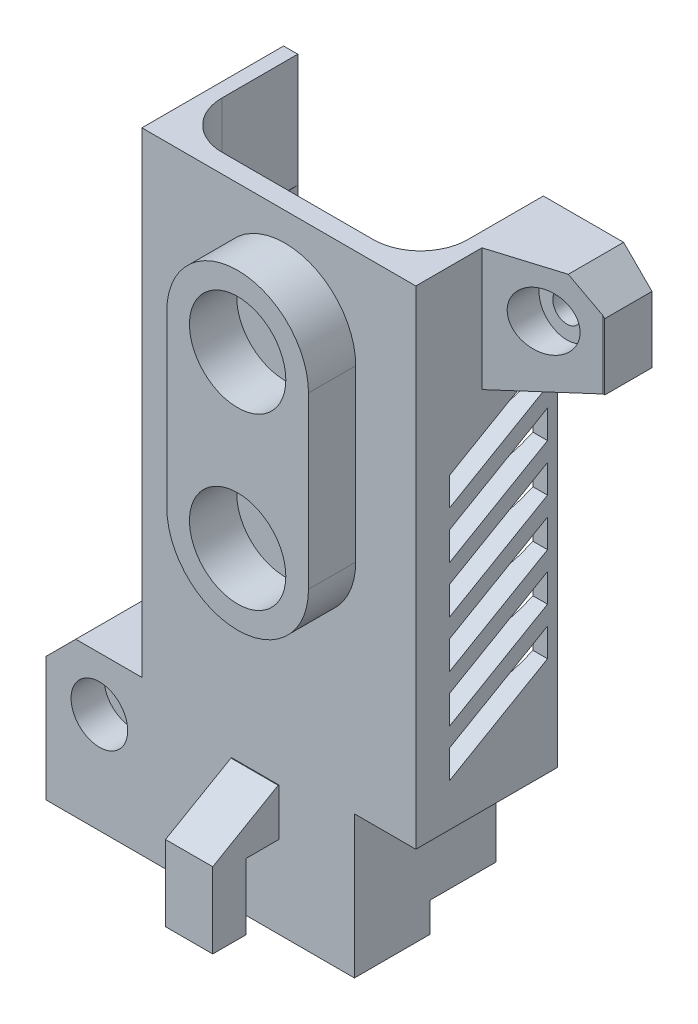
SolidWorks part; units mm, degrees
ref_plane "Přední rovina" through (0, 0, 0) normal (0, 0, 1) x (1, 0, 0)
ref_plane "Horní rovina" through (0, 0, 0) normal (0, 1, 0) x (1, 0, 0)
ref_plane "Pravá rovina" through (0, 0, 0) normal (1, 0, 0) x (0, 0, -1)
sketch "Skica2" plane through (0, 0, 0) normal (0, -1, 0) x (1, 0, 0)
  line L0 (8, 0) -> (6, 0)
  line L1 (-6, 0) -> (-8, 0)
  circle A0 centre (0, 0) radius 8 construction
  circle A1 centre (0, 0) radius 6 construction
  arc A2 (8, 0) -> (-8, 0) centre (0, 0) ccw
  arc A3 (6, 0) -> (-6, 0) centre (0, 0) ccw
extrude "Přidat vysunutím1" add sketch "Skica2" along normal up to surface (6 mm away)
sketch "Skica3" plane through (0, -9.7, 0) normal (0, -1, 0) x (1, 0, 0)
  line L0 (8, 0) -> (4.5, 0)
  line L1 (-4.5, 0) -> (-8, 0)
  line L2 (8, 0) -> (2, 0)
  line L3 (-2, 0) -> (-8, 0)
  circle A1 centre (0, 0) radius 8
  arc A2 (8, 0) -> (-8, 0) centre (0, 0) ccw
  arc A4 (2, 0) -> (-2, 0) centre (0, 0) ccw
  circle M2 centre (0, 0) radius 4.5
  circle M3 centre (0, 0) radius 8
  dimension "D1" = 0
extrude "Přidat vysunutím2" add sketch "Skica3" along normal up to surface (4 mm away) separate body contours A4 L2 L3 M2 | L1 L0 M2 M3 region at (6.25, -9.7, 0.1789) region at (0, -9.7, 2.171)
sketch "Skica4" plane through (0, 0, 0) normal (0, 0, -1) x (-1, 0, 0)
  circle A0 centre (-7.768, -14.6856) radius 4.1255
sketch "Skica6" plane through (0, -13.7, 0) normal (0, -1, 0) x (1, 0, 0)
  line L0 (-13, 0) -> (-8, 0)
  line L1 (8, 0) -> (13, 0)
  arc A0 (8, 0) -> (-8, 0) centre (0, 0) ccw construction
  arc A1 (8, 0) -> (-8, 0) centre (0, 0) ccw
  arc A2 (13, 0) -> (-13, 0) centre (0, 0) ccw
extrude "Přidat vysunutím3" add sketch "Skica6" against normal up to surface (18.7 mm away)
sketch "Skica7" plane through (0, 5, 0) normal (0, 1, 0) x (1, 0, 0)
  line L0 (-13, 0) -> (-14.5, 0)
  line L1 (-14.5, 0) -> (-14.5, -15)
  line L2 (-14.5, -15) -> (14.5, -15)
  line L3 (14.5, -15) -> (14.5, 0)
  line L4 (14.5, 0) -> (13, 0)
  arc A1 (-13, 0) -> (13, 0) centre (0, 0) ccw
extrude "Přidat vysunutím4" add sketch "Skica7" along normal up to surface (36 mm away) separate body
sketch "Skica8" plane through (0, 41, 0) normal (0, 1, 0) x (1, 0, 0)
  line L0 (-14.5, 0) -> (-13, 0) construction
  line L1 (13, 0) -> (21.5, 0) construction
  line L3 (-14.5, -15) -> (-14.5, 0) construction
  line L4 (14.5, -15) -> (-14.5, -15) construction
  line L5 (-14.5, 0) -> (-13, 0)
  line L6 (13, 0) -> (14.5, 0)
  line L7 (14.5, 0) -> (14.5, -15)
  line L8 (-14.5, -15) -> (-14.5, 0)
  line L9 (14.5, -15) -> (-14.5, -15)
  line L10 (-13, 0) -> (-13, -8)
  line L11 (-8, -13) -> (8, -13)
  line L12 (13, -8) -> (13, 0)
  arc A0 (-13, 0) -> (13, 0) centre (0, 0) ccw construction
  arc A1 (-13, -8) -> (-8, -13) centre (-8, -8) ccw
  arc A2 (8, -13) -> (13, -8) centre (8, -8) ccw
  dimension "D1" = 5
extrude "Přidat vysunutím5" add sketch "Skica8" along normal up to surface (12 mm away)
sketch "Skica9" plane through (0, 5, 0) normal (0, -1, 0) x (1, 0, 0)
  line L5 (13, 0) -> (14.5, 0)
  line L6 (14.5, 0) -> (14.5, 15)
  line L7 (14.5, 15) -> (-14.5, 15)
  line L8 (-14.5, 15) -> (-14.5, 0)
  line L9 (-14.5, 0) -> (-13, 0)
  line L10 (13, 0) -> (14.5, 0)
  line L11 (14.5, 0) -> (14.5, 15)
  line L12 (14.5, 15) -> (-14.5, 15)
  line L13 (-14.5, 15) -> (-14.5, 0)
  line L14 (-14.5, 0) -> (-13, 0)
  arc A1 (13, 0) -> (-13, 0) centre (0, 0) ccw
  arc A2 (13, 0) -> (-13, 0) centre (0, 0) ccw
  dimension "D1" = 0
extrude "Přidat vysunutím6" add sketch "Skica9" along normal up to surface (18.7 mm away) up to face at (0, -13.7, 3.75)
sketch "Skica10" plane through (0, 0, 0) normal (0, 0, -1) x (-1, 0, 0)
  line L0 (-14.5, -13.7) -> (-14.5, 53) construction
  line L1 (-14.5, 1.3549) -> (-8, 1.3549)
  line L2 (-14.5, 1.3549) -> (-14.5, -14.6856)
  line L3 (-14.5, -14.6856) -> (-8, -14.6856)
  line L4 (-8, 1.3549) -> (-8, -14.6856)
  line L5 (-14.5, 1.3549) -> (-8.0034, 1.3549) construction
  line L6 (-8, -6) -> (-8, -9.7) construction
extrude "Odebrat vysunutím2" cut sketch "Skica10" against normal up to surface (15 mm away) up to face at (0, 19.65, 15)
extrude "Odebrat vysunutím3" cut sketch "Skica4" against normal blind 7
sketch "Skica11" plane through (0, 0, 0) normal (0, 0, 1) x (1, 0, 0)
  line L17 (-24.65, -13.7) -> (-14.5, -13.7)
  line L18 (-14.5, -13.7) -> (-4.7569, -13.7)
  line L19 (-2.2431, -13.7) -> (-2, -13.7)
  line L20 (-2, -13.7) -> (-2, -9.7)
  line L21 (-2, -9.7) -> (-8, -9.7)
  line L22 (-8, -9.7) -> (-8, -6)
  line L23 (-8, -6) -> (-6, -6)
  line L24 (-6, -6) -> (-6, 0)
  line L25 (-6, 0) -> (-8, 0)
  line L26 (-8, 0) -> (-8, 5)
  line L27 (-8, 5) -> (-13, 5)
  line L28 (-13, 5) -> (-13, 10.9652)
  line L29 (-13, 10.9652) -> (-14.5, 10.9652)
  line L30 (-14.5, 10.9652) -> (-14.5, 2.6106)
  line L31 (-14.5, 2.6106) -> (-21.5034, 2.6106)
  line L32 (-21.5034, 2.6106) -> (-24.65, -0.5361)
  line L33 (-24.65, -0.5361) -> (-24.65, -13.7)
  line L34 (-24.65, -13.7) -> (-14.5, -13.7)
  line L35 (-14.5, -13.7) -> (-4.7569, -13.7)
  line L36 (-2.2431, -13.7) -> (-2, -13.7)
  line L37 (-2, -13.7) -> (-2, -9.7)
  line L38 (-2, -9.7) -> (-8, -9.7)
  line L39 (-8, -9.7) -> (-8, -6)
  line L40 (-8, -6) -> (-6, -6)
  line L41 (-6, -6) -> (-6, 0)
  line L42 (-6, 0) -> (-8, 0)
  line L43 (-8, 0) -> (-8, 5)
  line L44 (-8, 5) -> (-13, 5)
  line L45 (-13, 5) -> (-13, 10.9652)
  line L46 (-13, 10.9652) -> (-14.5, 10.9652)
  line L47 (-14.5, 10.9652) -> (-14.5, 2.6106)
  line L48 (-14.5, 2.6106) -> (-21.5034, 2.6106)
  line L49 (-21.5034, 2.6106) -> (-24.65, -0.5361)
  line L50 (-24.65, -0.5361) -> (-24.65, -13.7)
  arc A1 (-2.2431, -13.7) -> (-4.7569, -13.7) centre (-3.5, -18.5394) ccw
  arc A2 (-2.2431, -13.7) -> (-4.7569, -13.7) centre (-3.5, -18.5394) ccw
  circle A3 centre (-19, -3.0394) radius 1.6
  dimension "D1" = 0
extrude "Přidat vysunutím7" add sketch "Skica11" along normal up to surface (15 mm away) up to face at (2.6667, 13.5516, 15)
sketch "Skica12" plane through (0, 0, 0) normal (0, 0, -1) x (-1, 0, 0)
  circle A0 centre (3.5, -18.5394) radius 5
  dimension "D1" = 10
extrude "Odebrat vysunutím4" cut sketch "Skica12" against normal blind 10
sketch "Skica13" plane through (0, 0, 15) normal (0, 0, 1) x (1, 0, 0)
  circle A0 centre (-19, -3.0394) radius 3
  dimension "D1" = 6
extrude "Odebrat vysunutím5" cut sketch "Skica13" against normal blind 3.5
sketch "Skica14" plane through (14.5, 0, 0) normal (1, 0, 0) x (0, 0, -1)
  line L0 (-11.4494, 13.8487) -> (-1.0571, 19.8487)
  line L10 (-11.4494, 8.8487) -> (-1.0571, 14.8487)
  line L11 (-11.4494, 5.8487) -> (-11.4494, 8.8487)
  line L12 (-1.0571, 11.8487) -> (-11.4494, 5.8487)
  line L13 (-1.0571, 14.8487) -> (-1.0571, 11.8487)
  line L14 (-1.0571, 19.8487) -> (-1.0571, 16.8487)
  line L15 (-1.0571, 16.8487) -> (-11.4494, 10.8487)
  line L16 (-11.4494, 10.8487) -> (-11.4494, 13.8487)
  line L17 (-11.4494, 18.8487) -> (-1.0571, 24.8487)
  line L18 (-1.0571, 24.8487) -> (-1.0571, 21.8487)
  line L19 (-1.0571, 21.8487) -> (-11.4494, 15.8487)
  line L20 (-11.4494, 15.8487) -> (-11.4494, 18.8487)
  line L21 (-11.4494, 23.8487) -> (-1.0571, 29.8487)
  line L22 (-1.0571, 29.8487) -> (-1.0571, 26.8487)
  line L23 (-1.0571, 26.8487) -> (-11.4494, 20.8487)
  line L24 (-11.4494, 20.8487) -> (-11.4494, 23.8487)
  line L25 (-11.4494, 28.8487) -> (-1.0571, 34.8487)
  line L26 (-1.0571, 34.8487) -> (-1.0571, 31.8487)
  line L27 (-1.0571, 31.8487) -> (-11.4494, 25.8487)
  line L28 (-11.4494, 25.8487) -> (-11.4494, 28.8487)
  line L29 (-11.4494, 33.8487) -> (-1.0571, 39.8487)
  line L30 (-1.0571, 39.8487) -> (-1.0571, 36.8487)
  line L31 (-1.0571, 36.8487) -> (-11.4494, 30.8487)
  line L32 (-11.4494, 30.8487) -> (-11.4494, 33.8487)
  dimension "D1" = 6
extrude "Odebrat vysunutím6" cut sketch "Skica14" against normal up to surface (8.3428 mm away) up to face at (0, 26.6, 6.277)
sketch "Skica15" plane through (-14.5, 0, 0) normal (-1, 0, 0) x (0, 0, 1)
  line L0 (0, 10.9652) -> (0, 36.9652) construction
  circle A0 centre (-12, 35.9652) radius 1.5 construction
  circle A1 centre (-12, 11.9652) radius 1.5 construction
  arc A2 (0, 36.9652) -> (0, 10.9652) centre (0, 23.9652) ccw construction
  circle A6 centre (12, 35.9652) radius 1.5
  circle A7 centre (12, 11.9652) radius 1.5
extrude "Odebrat vysunutím7" cut sketch "Skica15" against normal up to surface (8 mm away)
sketch "Skica16" plane through (-14.5, 0, 0) normal (-1, 0, 0) x (0, 0, 1)
  line L0 (0, 10.9652) -> (0, 36.9652) construction
  arc A0 (0, 36.9652) -> (0, 10.9652) centre (0, 23.9652) ccw construction
  circle A1 centre (0, 23.9652) radius 13
extrude "Odebrat vysunutím8" cut sketch "Skica16" against normal up to surface (14.5 mm away) up to face at (-7.0789, 35.9027, 10.8818)
sketch "Skica17" plane through (14.5, 0, 0) normal (1, 0, 0) x (0, 0, -1)
  line L1 (0, 53) -> (-5, 53)
  line L2 (0, 53) -> (0, 43)
  line L3 (0, 43) -> (-5, 43)
  line L4 (-5, 53) -> (-5, 43)
  dimension "D1" = 10
  dimension "D2" = 5
extrude "Přidat vysunutím8" add sketch "Skica17" along normal blind 10
chamfer "Zkosení1" distance 3 angle 73 1 edges at (14.5, 43, 2.5) first distance on face at (14.5, 15.3487, 6.2533)
chamfer "Zkosení2" distance 3 angle 73 1 edges at (14.5, 46.5, 5) first distance on face at (14.5, 15.3487, 6.2533)
sketch "Skica18" plane through (0, 0, 0) normal (0, 0, -1) x (-1, 0, 0)
  line L0 (-24.5, 43) -> (-24.3126, 43) construction
  line L1 (-24.5, 53) -> (-14.5, 53) construction
  line L2 (-24.5, 53) -> (-24.5, 43) construction
  line L3 (-24.5, 43) -> (-14.5, 43) construction
  line L4 (-14.5, 53) -> (-14.5, 43) construction
  line L5 (-14.5, 53) -> (-24.5, 43) construction
  circle A0 centre (-19.5, 48) radius 1.5
  dimension "D2" = 3
  dimension "D1" = 10
extrude "Odebrat vysunutím9" cut sketch "Skica18" against normal blind 4
sketch "Skica19" plane through (0, 0, 4) normal (0, 0, -1) x (-1, 0, 0)
  circle A0 centre (-19.5, 48) radius 2.9551
extrude "Odebrat vysunutím10" cut sketch "Skica19" against normal blind 4
chamfer "Zkosení3" distance 3 angle 45 1 edges at (24.5, 53, 2.5)
sketch "Skica20" plane through (0, 0, 15) normal (0, 0, 1) x (1, 0, 0)
  line L1 (0, 0) -> (-5, 0)
  line L2 (0, 0) -> (0, -5)
  line L3 (0, -5) -> (-5, -5)
  line L4 (-5, 0) -> (-5, -5)
  dimension "D1" = 5
extrude "Přidat vysunutím9" add sketch "Skica20" along normal blind 7
sketch "Skica21" plane through (0, -5, 0) normal (0, -1, 0) x (1, 0, 0)
  line L0 (0, 22) -> (0, 15) construction
  line L1 (-5, 22) -> (0, 22)
  line L2 (-5, 22) -> (-5, 18.5)
  line L3 (-5, 18.5) -> (0, 18.5)
  line L4 (0, 22) -> (0, 18.5)
extrude "Přidat vysunutím10" add sketch "Skica21" along normal blind 7
chamfer "Zkosení4" distance 4 angle 60 1 edges at (-2.5, 0, 22) first distance on face at (-2.5, -6, 22)
sketch "Skica22" plane through (0, 0, 15) normal (0, 0, 1) x (1, 0, 0)
  line L0 (0.6352, 24.505) -> (0.6352, 42.505) construction
  line L1 (-6.8648, 24.505) -> (-6.8648, 42.505)
  line L2 (8.1352, 24.505) -> (8.1352, 42.505)
  circle A0 centre (0.6352, 42.505) radius 5.1
  circle A1 centre (0.6352, 24.505) radius 5.1
  arc A3 (-6.8648, 24.505) -> (8.1352, 24.505) centre (0.6352, 24.505) ccw
  arc A4 (8.1352, 42.505) -> (-6.8648, 42.505) centre (0.6352, 42.505) ccw
  point P4 (0.6352, 33.505)
  dimension "D1" = 10.2
  dimension "D2" = 7.5
  dimension "D3" = 18
extrude "Přidat vysunutím11" add sketch "Skica22" along normal blind 5
